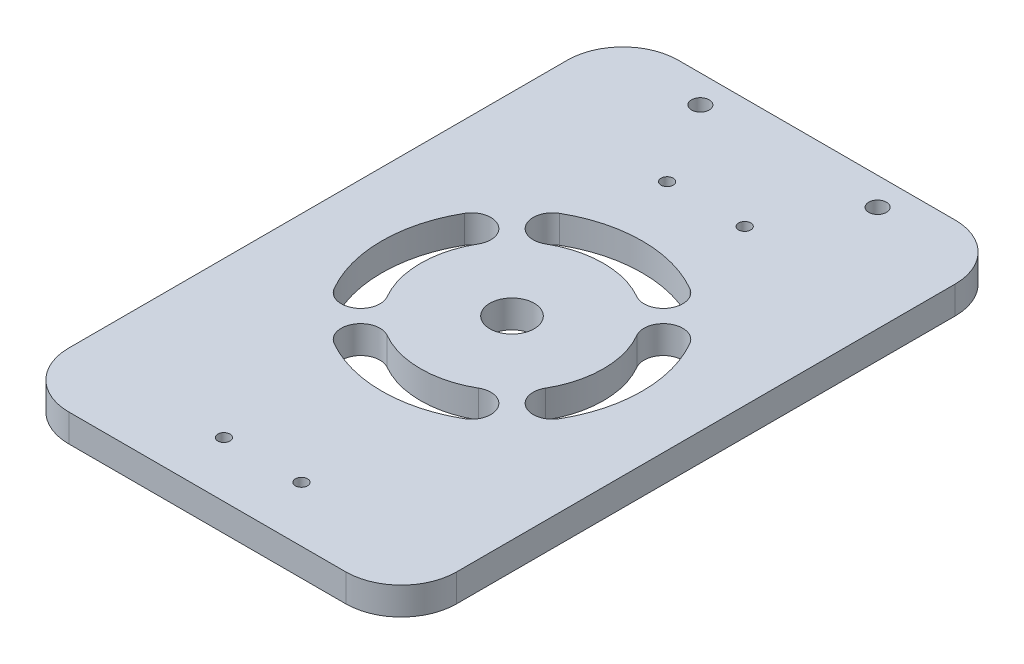
SolidWorks part; units mm, degrees
ref_plane "前视基准面" through (0, 0, 0) normal (0, 0, 1) x (1, 0, 0)
ref_plane "上视基准面" through (0, 0, 0) normal (0, 1, 0) x (1, 0, 0)
ref_plane "右视基准面" through (0, 0, 0) normal (1, 0, 0) x (0, 0, -1)
sketch "草图1" plane through (0, 0, 0) normal (0, 1, 0) x (1, 0, 0)
  line L0 (0, -113.2634) -> (0, 113.2634) construction
  line L1 (-35, 55) -> (35, 55)
  line L2 (-35, 55) -> (-35, -55)
  line L3 (-35, -55) -> (35, -55)
  line L4 (35, 55) -> (35, -55)
  line L5 (-35, 55) -> (35, -55) construction
  line L6 (-35, -55) -> (35, 55) construction
  circle A0 centre (-16, 50) radius 1.6
  circle A1 centre (-7, 35) radius 1.1
  circle A2 centre (-7, -45) radius 1.1
  circle A3 centre (7, -45) radius 1.1
  circle A4 centre (7, 35) radius 1.1
  circle A5 centre (16, 50) radius 1.6
  point P0 (0, 0)
  point P9 (0, 0)
  dimension "D4" = 3.2
  dimension "D6" = 2.2
  dimension "D8" = 2.2
  dimension "D1" = 70
  dimension "D2" = 110
  dimension "D3" = 5
  dimension "D5" = 16
  dimension "D7" = 7
  dimension "D9" = 80
  dimension "D10" = 10
extrude "凸台-拉伸1" add sketch "草图1" along normal blind 5
fillet "圆角1" radius 10 4 edges at (-35, 2.5, 55) (35, 2.5, 55) (35, 2.5, -55) (-35, 2.5, -55)
sketch "草图3" plane through (0, 0, 0) normal (0, 1, 0) x (1, 0, 0)
  line L0 (-17.3205, 10) -> (0, 0) construction
  line L1 (0, 0) -> (-17.3205, -10) construction
  line L2 (0, 0) -> (0, 10.0749) construction
  circle A0 centre (0, 0) radius 20 construction
  arc A1 (-17.3205, 10) -> (-17.3205, -10) centre (0, 0) ccw construction
  arc A2 (-20.3516, 11.75) -> (-20.3516, -11.75) centre (0, 0) ccw
  arc A3 (-14.2894, 8.25) -> (-14.2894, -8.25) centre (0, 0) ccw
  arc A4 (-14.2894, 8.25) -> (-20.3516, 11.75) centre (-17.3205, 10) ccw
  arc A5 (-20.3516, -11.75) -> (-14.2894, -8.25) centre (-17.3205, -10) ccw
  arc A6 (10, 17.3205) -> (-10, 17.3205) centre (0, 0) ccw construction
  arc A7 (11.75, 20.3516) -> (-11.75, 20.3516) centre (0, 0) ccw
  arc A8 (8.25, 14.2894) -> (-8.25, 14.2894) centre (0, 0) ccw
  arc A9 (8.25, 14.2894) -> (11.75, 20.3516) centre (10, 17.3205) ccw
  arc A10 (-11.75, 20.3516) -> (-8.25, 14.2894) centre (-10, 17.3205) ccw
  arc A11 (17.3205, -10) -> (17.3205, 10) centre (0, 0) ccw construction
  arc A12 (20.3516, -11.75) -> (20.3516, 11.75) centre (0, 0) ccw
  arc A13 (14.2894, -8.25) -> (14.2894, 8.25) centre (0, 0) ccw
  arc A14 (14.2894, -8.25) -> (20.3516, -11.75) centre (17.3205, -10) ccw
  arc A15 (20.3516, 11.75) -> (14.2894, 8.25) centre (17.3205, 10) ccw
  arc A16 (-10, -17.3205) -> (10, -17.3205) centre (0, 0) ccw construction
  arc A17 (-11.75, -20.3516) -> (11.75, -20.3516) centre (0, 0) ccw
  arc A18 (-8.25, -14.2894) -> (8.25, -14.2894) centre (0, 0) ccw
  arc A19 (-8.25, -14.2894) -> (-11.75, -20.3516) centre (-10, -17.3205) ccw
  arc A20 (11.75, -20.3516) -> (8.25, -14.2894) centre (10, -17.3205) ccw
  circle A21 centre (0, 0) radius 4
  point P5 (-20, 0)
  point P19 (0, 20)
  point P26 (20, 0)
  point P33 (0, -20)
  point P38 (0, 0)
  dimension "D1" = 60
  dimension "D3" = 3.5
  dimension "D5" = 8
  dimension "D2" = 60
  dimension "D4" = 4
extrude "切除-拉伸2" cut sketch "草图3" along normal blind 5
